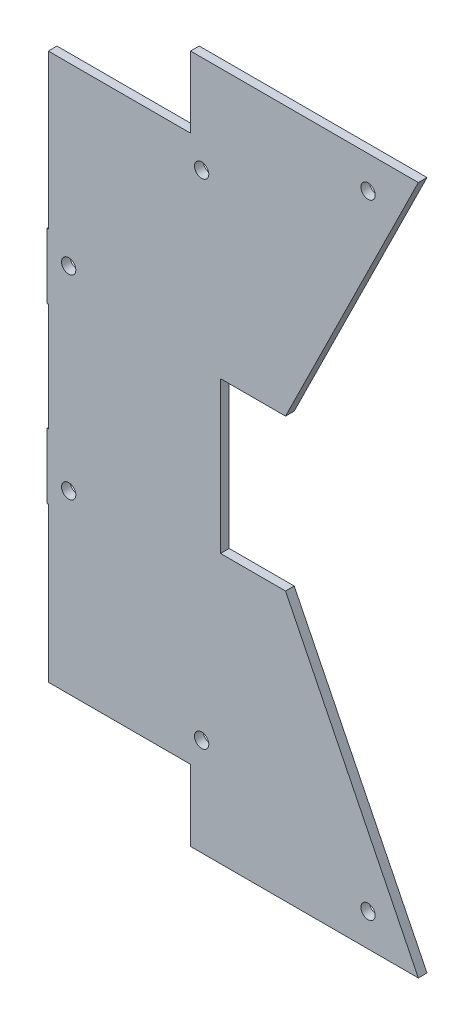
SolidWorks part; units mm, degrees
material "Thornel Mat VMA"
ref_plane "Front Plane" through (0, 0, 0) normal (0, 0, 1) x (1, 0, 0)
ref_plane "Top Plane" through (0, 0, 0) normal (0, 1, 0) x (1, 0, 0)
ref_plane "Right Plane" through (0, 0, 0) normal (1, 0, 0) x (0, 0, -1)
sketch "Sketch1" plane through (0, 0, 0) normal (0, 0, 1) x (1, 0, 0)
  line L0 (-2.9301, -104.5098) -> (-3.3149, -104.5098)
  line L1 (-3.3149, -72.8868) -> (-2.9301, -72.8868)
  line L78 (47.4851, -66.5368) -> (47.4851, -72.8868)
  line L79 (47.4851, -104.5098) -> (47.4851, -110.8598)
  line L80 (66.5174, -66.5368) -> (105.3971, 12.1397)
  line L81 (105.3971, 12.1397) -> (38.7094, 12.1397)
  line L88 (38.7094, 12.1397) -> (38.7094, -8.6883)
  line L89 (-2.9301, -8.6883) -> (38.7094, -8.6883)
  line L90 (-3.3149, -53.8368) -> (-2.9301, -53.8368)
  line L91 (-2.9301, -53.8368) -> (-2.9301, -8.6883)
  line L92 (-3.3149, -66.5368) -> (-3.3149, -53.8368)
  line L93 (-3.3149, -72.8868) -> (-3.3149, -66.5368)
  line L94 (-2.9301, -104.5098) -> (-2.9301, -72.8868)
  line L95 (-3.3149, -110.8598) -> (-3.3149, -104.5098)
  line L96 (66.5174, -110.8598) -> (105.3971, -189.5363)
  line L97 (105.3971, -189.5363) -> (38.7094, -189.5363)
  line L98 (38.7094, -189.5363) -> (38.7094, -168.7083)
  line L99 (-2.9301, -168.7083) -> (38.7094, -168.7083)
  line L106 (-3.3149, -110.8598) -> (-3.3149, -123.5598)
  line L107 (-3.3149, -123.5598) -> (-2.9301, -123.5598)
  line L108 (66.5174, -110.8598) -> (47.4851, -110.8598)
  line L109 (47.4851, -66.5368) -> (66.5174, -66.5368)
  line L110 (47.4851, -104.5098) -> (47.4851, -72.8868)
  line L111 (-2.9301, -123.5598) -> (-2.9301, -168.7083)
  circle A0 centre (90.6739, 2.6147) radius 2.0955
  circle A1 centre (41.9566, -16.4353) radius 2.0955
  circle A2 centre (3.0351, -60.1868) radius 2.0955
  circle A3 centre (3.0351, -117.2098) radius 2.0955
  circle A4 centre (41.9566, -160.9613) radius 2.0955
  circle A5 centre (90.6739, -180.0113) radius 2.0955
  point P2 (90.6739, 2.6147)
  point P4 (41.9566, -16.4353)
  point P6 (3.0351, -60.1868)
  point P8 (3.0351, -117.2098)
  point P10 (41.9566, -160.9613)
  point P11 (90.6739, -180.0113)
  dimension "D2" = 4.191
  dimension "D1" = 66.6876
extrude "Boss-Extrude1" add sketch "Sketch1" along normal blind 2.54
